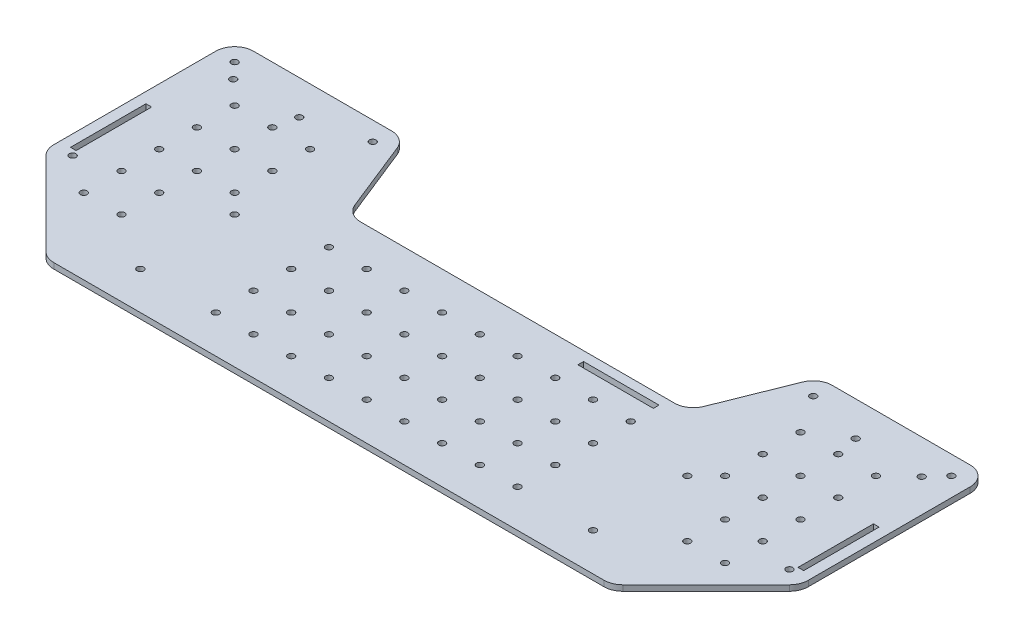
SolidWorks part; units mm, degrees
ref_plane "前视基准面" through (0, 0, 0) normal (0, 0, 1) x (1, 0, 0)
ref_plane "上视基准面" through (0, 0, 0) normal (0, 1, 0) x (1, 0, 0)
ref_plane "右视基准面" through (0, 0, 0) normal (1, 0, 0) x (0, 0, -1)
other "Configuration Table"
sketch "草图1" plane through (0, 0, 0) normal (0, 1, 0) x (1, 0, 0)
  line L0 (-197.0711, -27.9289) -> (-152.9289, -72.0711)
  line L1 (-145.8579, -75) -> (145.8579, -75)
  line L2 (-200, -20.8579) -> (-200, 65)
  line L3 (-190, 75) -> (-116.7703, 75)
  line L4 (200, -20.8579) -> (200, 65)
  line L5 (-200, -75) -> (200, 75) construction
  line L6 (-200, 75) -> (200, -75) construction
  line L7 (152.9289, -72.0711) -> (197.0711, -27.9289)
  line L8 (-107.4856, 68.7139) -> (-92.5144, 31.2861)
  line L9 (-83.2297, 25) -> (83.2297, 25)
  line L10 (107.4856, 68.7139) -> (92.5144, 31.2861)
  line L11 (116.7703, 75) -> (190, 75)
  arc A0 (107.4856, 68.7139) -> (116.7703, 75) centre (116.7703, 65) cw
  arc A1 (92.5144, 31.2861) -> (83.2297, 25) centre (83.2297, 35) cw
  arc A2 (-92.5144, 31.2861) -> (-83.2297, 25) centre (-83.2297, 35) ccw
  arc A3 (-107.4856, 68.7139) -> (-116.7703, 75) centre (-116.7703, 65) ccw
  arc A4 (190, 75) -> (200, 65) centre (190, 65) cw
  arc A5 (-200, 65) -> (-190, 75) centre (-190, 65) cw
  arc A6 (197.0711, -27.9289) -> (200, -20.8579) centre (190, -20.8579) ccw
  arc A7 (152.9289, -72.0711) -> (145.8579, -75) centre (145.8579, -65) cw
  arc A8 (-197.0711, -27.9289) -> (-200, -20.8579) centre (-190, -20.8579) cw
  arc A9 (-152.9289, -72.0711) -> (-145.8579, -75) centre (-145.8579, -65) ccw
  point P0 (0, 0)
  point P14 (0, 25)
  dimension "D4" = 10
  dimension "D5" = 10
  dimension "D1" = 400
  dimension "D2" = 150
  dimension "D3" = 50
extrude "凸台-拉伸1" add sketch "草图1" along normal blind 3
sketch "草图2" plane through (0, 0, 0) normal (0, -1, 0) x (1, 0, 0)
  line L0 (0, 0) -> (0, 50000) construction
  circle A0 centre (120, 5) radius 1.75
  circle A1 centre (120, 55) radius 1.75
  circle A2 centre (-120, 55) radius 1.75
  circle A3 centre (-120, 5) radius 1.75
extrude "切除-拉伸1" cut sketch "草图2" against normal blind 59
sketch "草图3" plane through (0, 3, 0) normal (0, 1, 0) x (1, 0, 0)
  line L0 (0, 0) -> (0, 50000) construction
  circle A0 centre (116.7703, 65) radius 1.75
  circle A1 centre (190, 65) radius 1.75
  circle A2 centre (-190, 65) radius 1.75
  circle A3 centre (-116.7703, 65) radius 1.75
  circle A4 centre (-190, -20.8579) radius 1.75
  circle A5 centre (190, -20.8579) radius 1.75
  dimension "D1" = 3.5
  dimension "D2" = 3.5
  dimension "D3" = 3.5
extrude "切除-拉伸2" cut sketch "草图3" against normal blind 59
sketch "草图4" plane through (0, 0, 0) normal (0, -1, 0) x (1, 0, 0)
  line L2 (0, 0) -> (0, -50000) construction
  line L3 (-1137.5, -55) -> (0, -55) construction
  line L4 (137.5, -48) -> (137.5, -62) construction
  line L5 (192.5, -62) -> (192.5, -48) construction
  line L6 (182.5, -55) -> (182.5, -65) construction
  line L8 (175.5, -65) -> (189.5, -65) construction
  line L9 (147.5, -55) -> (147.5, -65) construction
  line L11 (140.5, -65) -> (154.5, -65) construction
  line L12 (147.5, -55) -> (182.5, -55) construction
  circle A0 centre (147.5, -56.75) radius 1.75
  circle A1 centre (182.5, -56.75) radius 1.75
  circle A2 centre (-182.5, -56.75) radius 1.75
  circle A3 centre (-147.5, -56.75) radius 1.75
  point P15 (137.5, -55)
  point P18 (192.5, -55)
  dimension "D1" = 3.5
  dimension "D2" = 3.5
sketch "草图5" plane through (0, 3, 0) normal (0, 1, 0) x (1, 0, 0)
  line L0 (0, 0) -> (0, 50000) construction
  line L1 (83.2297, 25) -> (-83.2297, 25) construction
  circle A0 centre (-20, 5) radius 1.75
  circle A1 centre (-20, -15) radius 1.75
  circle A2 centre (-20, -35) radius 1.75
  circle A3 centre (-20, -55) radius 1.75
  circle A4 centre (-40, 5) radius 1.75
  circle A5 centre (-40, -15) radius 1.75
  circle A6 centre (-40, -35) radius 1.75
  circle A7 centre (-40, -55) radius 1.75
  circle A8 centre (-60, 5) radius 1.75
  circle A9 centre (-60, -15) radius 1.75
  circle A10 centre (-60, -35) radius 1.75
  circle A11 centre (-60, -55) radius 1.75
  circle A12 centre (-80, 5) radius 1.75
  circle A13 centre (-80, -15) radius 1.75
  circle A14 centre (-80, -35) radius 1.75
  circle A15 centre (-80, -55) radius 1.75
  circle A16 centre (80, -55) radius 1.75
  circle A17 centre (80, -35) radius 1.75
  circle A18 centre (80, -15) radius 1.75
  circle A19 centre (80, 5) radius 1.75
  circle A20 centre (60, -55) radius 1.75
  circle A21 centre (60, -35) radius 1.75
  circle A22 centre (60, -15) radius 1.75
  circle A23 centre (60, 5) radius 1.75
  circle A24 centre (40, -55) radius 1.75
  circle A25 centre (40, -35) radius 1.75
  circle A26 centre (40, -15) radius 1.75
  circle A27 centre (40, 5) radius 1.75
  circle A28 centre (20, -55) radius 1.75
  circle A29 centre (20, -35) radius 1.75
  circle A30 centre (20, -15) radius 1.75
  circle A31 centre (20, 5) radius 1.75
  dimension "D1" = 20
  dimension "D2" = 20
  dimension "D3" = 3.5
  dimension "D4" = 4
  dimension "D5" = 4
extrude "切除-拉伸4" cut sketch "草图5" against normal blind 10
sketch "草图6" plane through (0, 3, 0) normal (0, 1, 0) x (1, 0, 0)
  line L0 (0, 0) -> (0, 50000) construction
  circle A5 centre (-170, 45) radius 1.75
  circle A6 centre (-150, 45) radius 1.75
  circle A7 centre (-130, 45) radius 1.75
  circle A9 centre (-170, 25) radius 1.75
  circle A10 centre (-150, 25) radius 1.75
  circle A11 centre (-130, 25) radius 1.75
  circle A13 centre (-170, 5) radius 1.75
  circle A14 centre (-150, 5) radius 1.75
  circle A15 centre (-130, 5) radius 1.75
  circle A16 centre (-170, -15) radius 1.75
  circle A17 centre (-150, -15) radius 1.75
  circle A18 centre (-170, -35) radius 1.75
  circle A19 centre (-150, -35) radius 1.75
  circle A20 centre (150, -35) radius 1.75
  circle A21 centre (170, -35) radius 1.75
  circle A22 centre (150, -15) radius 1.75
  circle A23 centre (170, -15) radius 1.75
  circle A24 centre (130, 5) radius 1.75
  circle A25 centre (150, 5) radius 1.75
  circle A26 centre (170, 5) radius 1.75
  circle A28 centre (130, 25) radius 1.75
  circle A29 centre (150, 25) radius 1.75
  circle A30 centre (170, 25) radius 1.75
  circle A32 centre (130, 45) radius 1.75
  circle A33 centre (150, 45) radius 1.75
  circle A34 centre (170, 45) radius 1.75
  dimension "D1" = 3
extrude "切除-拉伸5" cut sketch "草图6" against normal blind 10
sketch "草图7" plane through (0, 3, 0) normal (0, 1, 0) x (1, 0, 0)
  line L0 (40, 5) -> (-49960, 5) construction
  line L1 (0, 5) -> (0, -50000) construction
  circle A0 centre (0, 5) radius 1.75
  circle A1 centre (0, -15) radius 1.75
  circle A2 centre (0, -35) radius 1.75
  circle A3 centre (0, -55) radius 1.75
  dimension "D1" = 3.5
  dimension "D2" = 4
extrude "切除-拉伸6" cut sketch "草图7" against normal blind 10
extrude "切除-拉伸3" cut sketch "草图4" against normal blind 59
sketch "草图8" plane through (0, 3, 0) normal (0, 1, 0) x (1, 0, 0)
  line L0 (0, 0) -> (0, 50000) construction
  line L1 (191.36, 22.35) -> (194.36, 22.35)
  line L2 (191.36, 22.35) -> (191.36, -17.65)
  line L3 (191.36, -17.65) -> (194.36, -17.65)
  line L4 (194.36, 22.35) -> (194.36, -17.65)
  line L5 (-194.36, 22.35) -> (-194.36, -17.65)
  line L6 (-191.36, -17.65) -> (-194.36, -17.65)
  line L7 (-191.36, 22.35) -> (-191.36, -17.65)
  line L8 (-191.36, 22.35) -> (-194.36, 22.35)
extrude "切除-拉伸7" cut sketch "草图8" against normal blind 3
sketch "草图9" plane through (0, 3, 0) normal (0, 1, 0) x (1, 0, 0)
  line L0 (0, 0) -> (0, 50000) construction
  line L1 (80, 20) -> (40, 20)
  line L2 (80, 20) -> (80, 17)
  line L3 (80, 17) -> (40, 17)
  line L4 (40, 20) -> (40, 17)
  line L5 (80, 20) -> (40, 17) construction
  line L6 (80, 17) -> (40, 20) construction
  line L7 (83.2297, 25) -> (-83.2297, 25) construction
  point P0 (60, 18.5)
  point P10 (0, 0)
  dimension "D1" = 3
  dimension "D2" = 40
  dimension "D3" = 5
  dimension "D4" = 60
extrude "切除-拉伸8" cut sketch "草图9" against normal blind 4
